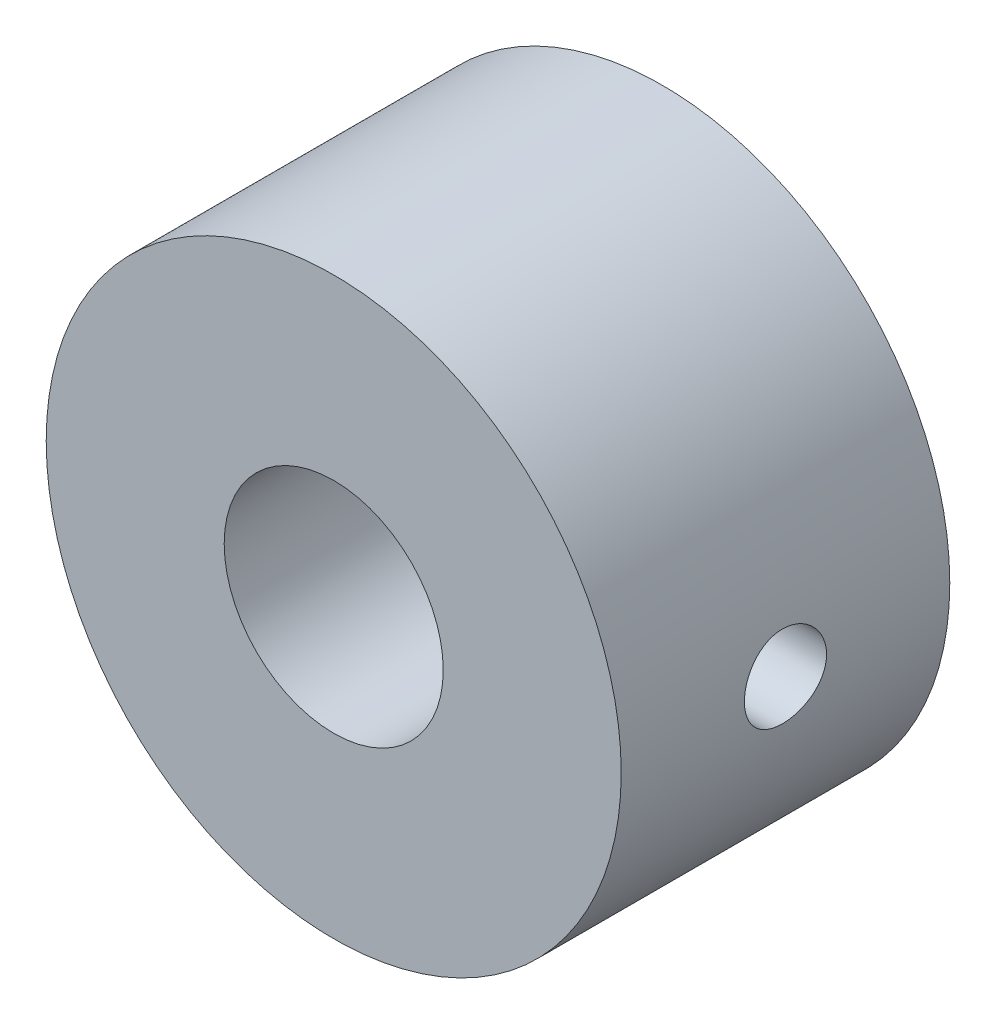
SolidWorks part; units mm, degrees
ref_plane "Front Plane" through (0, 0, 0) normal (0, 0, 1) x (1, 0, 0)
ref_plane "Top Plane" through (0, 0, 0) normal (0, 1, 0) x (1, 0, 0)
ref_plane "Right Plane" through (0, 0, 0) normal (1, 0, 0) x (0, 0, -1)
sketch "Sketch1" plane through (0, 0, 0) normal (0, 0, 1) x (1, 0, 0)
  circle A0 centre (0, 0) radius 10.5
  dimension "D1" = 21
extrude "Boss-Extrude1" add sketch "Sketch1" along normal blind 12
sketch "Sketch2" plane through (0, 0, 12) normal (0, 0, 1) x (1, 0, 0)
  circle A0 centre (0, 0) radius 4
  dimension "D1" = 8
extrude "Cut-Extrude1" cut sketch "Sketch2" against normal blind 15
sketch "Sketch3" plane through (0, 0, 0) normal (1, 0, 0) x (0, 0, -1)
  line L0 (-12, 0) -> (0, 0) construction
  line L1 (-12, 10.5) -> (-12, -10.5) construction
  line L2 (0, -10.5) -> (0, 10.5) construction
  circle A0 centre (-6, 0) radius 1.5
  dimension "D1" = 3
extrude "Cut-Extrude2" cut sketch "Sketch3" against normal through all both and the other way through all
